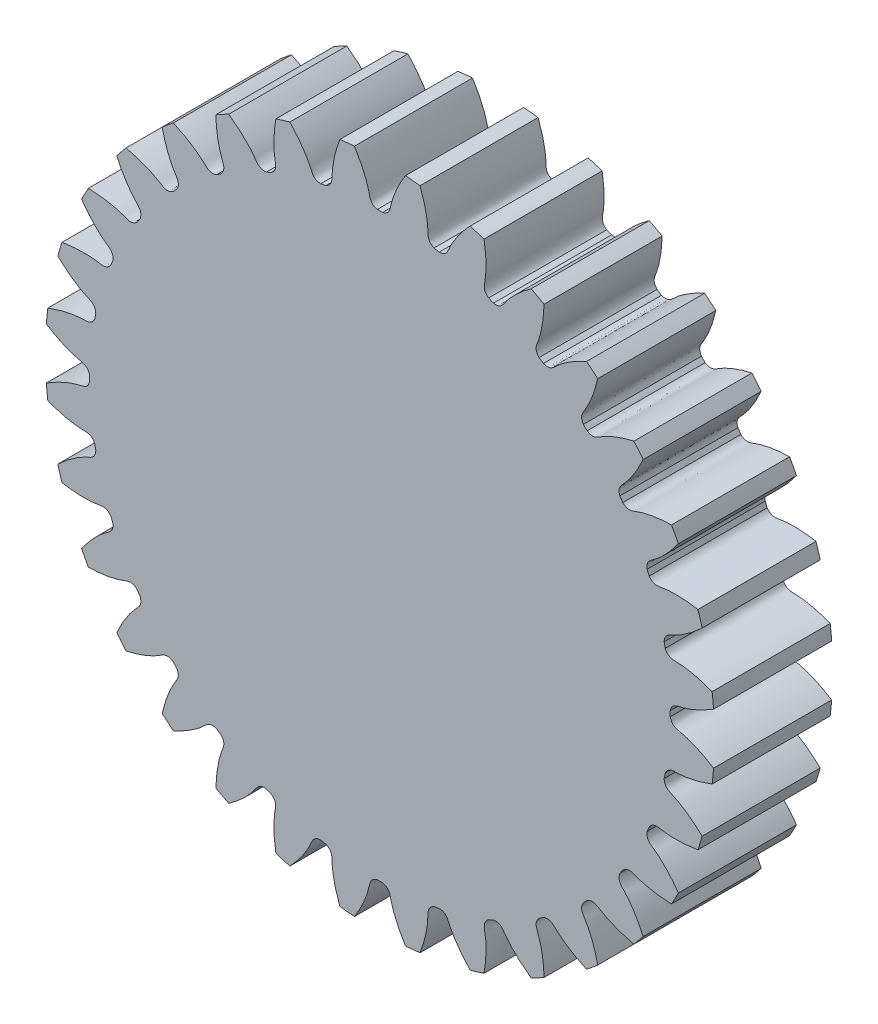
SolidWorks part; units mm, degrees
ref_plane "前视基准面" through (0, 0, 0) normal (0, 0, 1) x (1, 0, 0)
ref_plane "上视基准面" through (0, 0, 0) normal (0, 1, 0) x (1, 0, 0)
ref_plane "右视基准面" through (0, 0, 0) normal (1, 0, 0) x (0, 0, -1)
other "Configuration Table"
sketch "草图1" plane through (0, 0, 0) normal (0, 0, 1) x (1, 0, 0)
  circle A0 centre (0, 0) radius 8.5
extrude "凸台-拉伸1" add sketch "草图1" along normal blind 3
ref_axis "基准轴1" through (0, 0, 3) along (0, 0, -1)
sketch "草图2" plane through (0, 0, 0) normal (0, 0, 1) x (1, 0, 0)
  line L0 (0, 0) -> (0, 8.5) construction
  circle A0 centre (0, 0) radius 8.5 construction
  arc A1 (0.067, 7.3747) -> (-0.067, 7.3747) centre (0, 0) ccw
  arc A2 (1.6765, 9.6348) -> (-1.6765, 9.6348) centre (0, 0) ccw
  spline S0 degree 3 poles (0.067, 7.3747) (0.2444, 7.4176) (0.2542, 7.5462) (0.2867, 7.6804) (0.2952, 7.7127) (0.3051, 7.7477) (0.3166, 7.7854) (0.3299, 7.8257) (0.3449, 7.8686) (0.3618, 7.9139) (0.3807, 7.9618) (0.4017, 8.012) (0.4249, 8.0645) (0.4505, 8.1193) (0.4785, 8.1763) (0.509, 8.2353) (0.5421, 8.2964) (0.5779, 8.3594) (0.6164, 8.4243) (0.6579, 8.491) (0.7023, 8.5593) (0.7498, 8.6292) (0.8004, 8.7006) (0.8542, 8.7734) (0.9113, 8.8475) (0.9717, 8.9228) (1.0356, 8.9992) (1.1029, 9.0765) (1.1738, 9.1547) (1.2483, 9.2337) (1.3265, 9.3133) (1.4084, 9.3934) (1.5241, 9.5022) (1.6145, 9.5821) (1.6765, 9.6348) knots 0 0 0 0 0.124533 0.135329 0.147193 0.160126 0.174128 0.189198 0.205337 0.222544 0.24082 0.260164 0.280577 0.302059 0.324609 0.348227 0.372914 0.39867 0.425494 0.453386 0.482348 0.512377 0.543476 0.575642 0.608878 0.643181 0.678554 0.714995 0.752504 0.791082 0.830729 0.871444 0.913227 1 1 1 1
  spline S1 degree 3 poles (-0.067, 7.3747) (-0.2444, 7.4176) (-0.2542, 7.5462) (-0.2867, 7.6804) (-0.2952, 7.7127) (-0.3051, 7.7477) (-0.3166, 7.7854) (-0.3299, 7.8257) (-0.3449, 7.8686) (-0.3618, 7.9139) (-0.3807, 7.9618) (-0.4017, 8.012) (-0.4249, 8.0645) (-0.4505, 8.1193) (-0.4785, 8.1763) (-0.509, 8.2353) (-0.5421, 8.2964) (-0.5779, 8.3594) (-0.6164, 8.4243) (-0.6579, 8.491) (-0.7023, 8.5593) (-0.7498, 8.6292) (-0.8004, 8.7006) (-0.8542, 8.7734) (-0.9113, 8.8475) (-0.9717, 8.9228) (-1.0356, 8.9992) (-1.1029, 9.0765) (-1.1738, 9.1547) (-1.2483, 9.2337) (-1.3265, 9.3133) (-1.4084, 9.3934) (-1.5241, 9.5022) (-1.6145, 9.5821) (-1.6765, 9.6348) knots 0 0 0 0 0.124533 0.135329 0.147193 0.160126 0.174128 0.189198 0.205337 0.222544 0.24082 0.260164 0.280577 0.302059 0.324609 0.348227 0.372914 0.39867 0.425494 0.453386 0.482348 0.512377 0.543476 0.575642 0.608878 0.643181 0.678554 0.714995 0.752504 0.791082 0.830729 0.871444 0.913227 1 1 1 1
extrude "切除-拉伸1" cut sketch "草图2" along normal through all
pattern_circular "阵列(圆周)1" count 32 every 11.25 about axis through (0, 0, 3) along (0, 0, -1) of "切除-拉伸1"
sketch "草图3" plane through (0, 0, 0) normal (0, 0, 1) x (1, 0, 0)
  circle A0 centre (0, 0) radius 8 construction
  dimension "Dn" = 16
